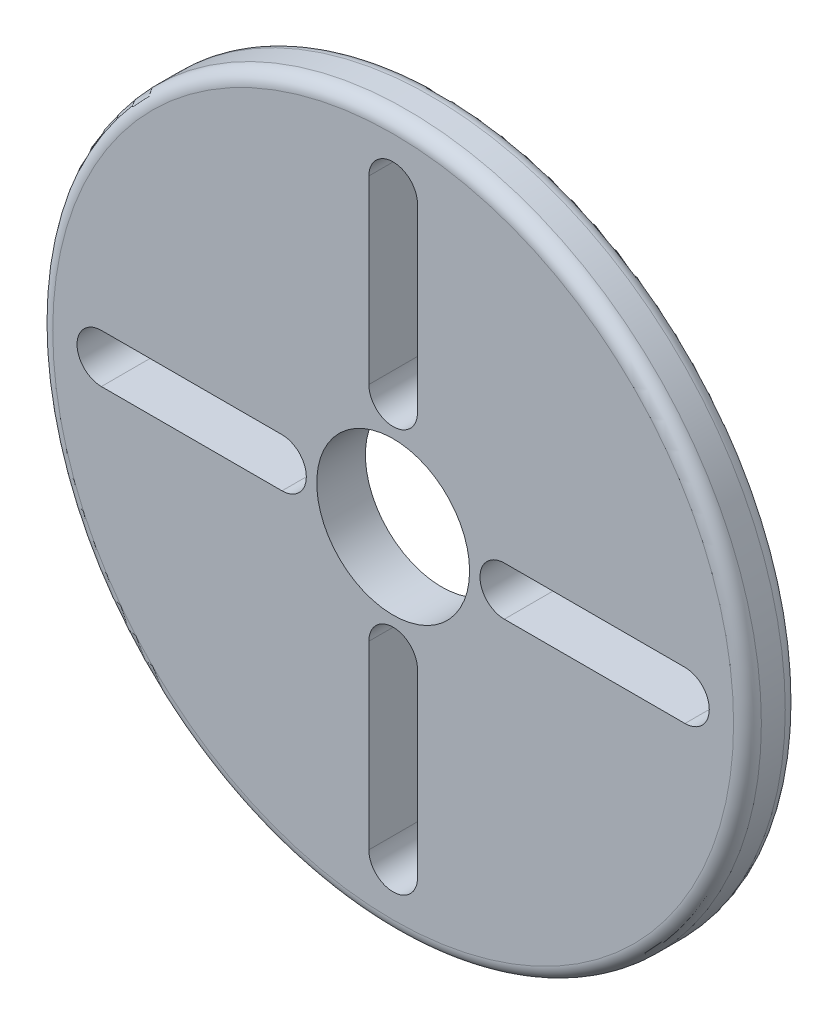
SolidWorks part; units mm, degrees
material "ABS"
ref_plane "Front Plane" through (0, 0, 0) normal (0, 0, 1) x (1, 0, 0)
ref_plane "Top Plane" through (0, 0, 0) normal (0, 1, 0) x (1, 0, 0)
ref_plane "Right Plane" through (0, 0, 0) normal (1, 0, 0) x (0, 0, -1)
sketch "Sketch1" plane through (0, 0, 0) normal (0, 0, 1) x (1, 0, 0)
  circle A0 centre (0, 0) radius 5.5
  circle A2 centre (0, 0) radius 25.5
  dimension "D1" = 11
  dimension "D2" = 20
extrude "Boss-Extrude1" add sketch "Sketch1" along normal blind 3.5
sketch "Sketch8" plane through (0, 0, 0) normal (0, 1, 0) x (1, 0, 0)
  line L0 (25.5, 0) -> (-25.5, 0) construction
  line L1 (25.5, 0) -> (-11.5, 0) construction
  line L2 (0, 0) -> (0, -17.1822) construction
  line L3 (-11.5, 0) -> (-11.5, 3.5)
  line L4 (-11.5, 3.5) -> (25.5, 0) construction
  line L5 (11.5, 3.5) -> (-25.5, 0) construction
  line L6 (11.5, 0) -> (11.5, 3.5) construction
  line L7 (11.5, 0) -> (-25.5, 0) construction
  line L8 (-11.5, 3.5) -> (-25.5, 0)
  line L9 (-25.5, 0) -> (-11.5, 0)
  point P10 (11.5, 1.75)
  dimension "D1" = 23
  dimension "D2" = 3.5
revolve "Revolve2" add sketch "Sketch8" angle 360 about L2
sketch "Sketch7" plane through (0, 0, 0) normal (0, 0, 1) x (1, 0, 0)
  line L0 (1.75, -8) -> (1.75, -21)
  line L1 (-1.75, -8) -> (-1.75, -21)
  line L2 (-8, -1.75) -> (-21, -1.75)
  line L3 (-8, 1.75) -> (-21, 1.75)
  line L4 (-1.75, 8) -> (-1.75, 21)
  line L5 (1.75, 8) -> (1.75, 21)
  line L6 (8, 1.75) -> (21, 1.75)
  line L7 (8, -1.75) -> (21, -1.75)
  circle A0 centre (0, 0) radius 8 construction
  arc A1 (1.75, -8) -> (-1.75, -8) centre (0, -8) ccw
  arc A5 (-8, -1.75) -> (-8, 1.75) centre (-8, 0) ccw
  arc A6 (-1.75, 8) -> (1.75, 8) centre (0, 8) ccw
  arc A7 (8, 1.75) -> (8, -1.75) centre (8, 0) ccw
  arc A8 (-1.75, -21) -> (1.75, -21) centre (0, -21) ccw
  arc A9 (-21, 1.75) -> (-21, -1.75) centre (-21, 0) ccw
  arc A10 (1.75, 21) -> (-1.75, 21) centre (0, 21) ccw
  arc A11 (21, -1.75) -> (21, 1.75) centre (21, 0) ccw
  point P4 (-17.1274, 0)
  point P7 (-8, -1.75)
  point P14 (0, 0)
  point P15 (0, 0)
  point P35 (0, 0)
  dimension "D1" = 16
  dimension "D2" = 3.5
  dimension "D4" = 13
  dimension "D3" = 4
  dimension "D5" = 4
extrude "Cut-Extrude1" cut sketch "Sketch7" along normal through all both and the other way through all contours A7 | A1 L1 A8 L0 | A6 L5 A10 L4 | A5 L3 A9 L2 region at (14.5, 0, 0)
fillet "Fillet2" radius 1 2 edges at (25.5, 0, 3.5) (-25.5, 0, 0)
